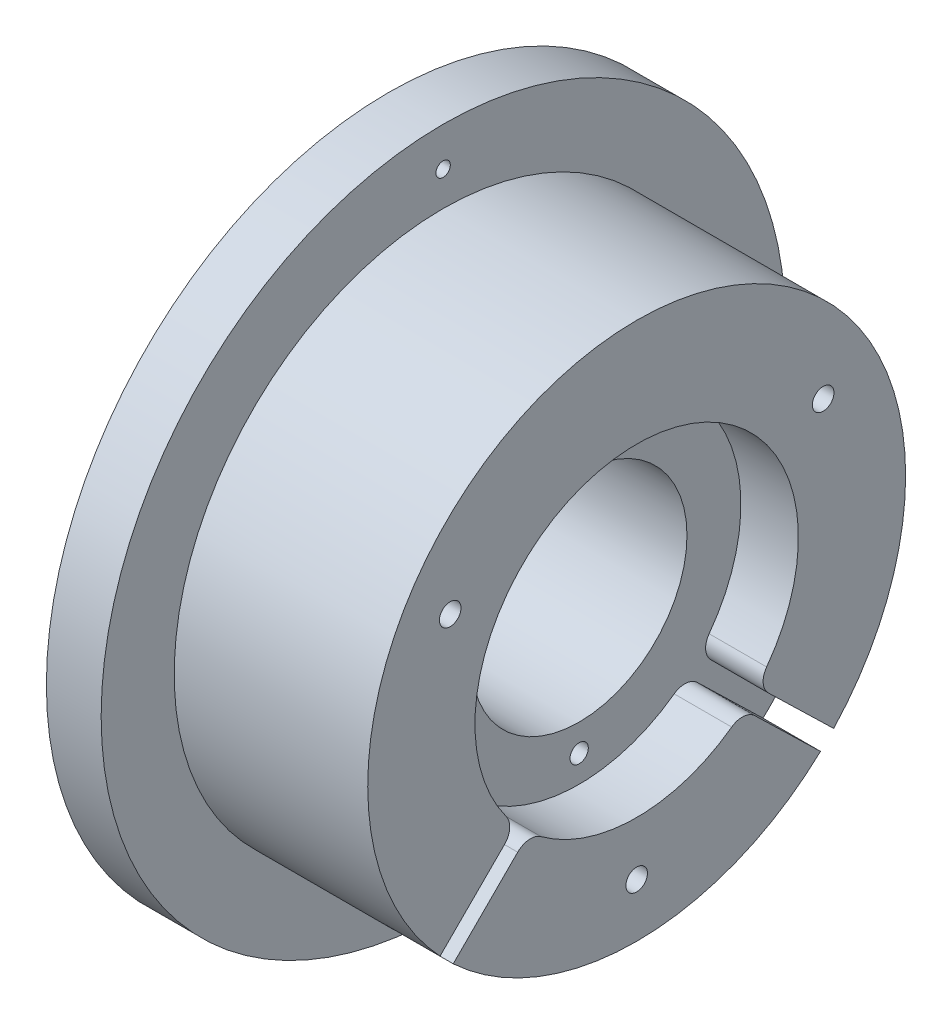
SolidWorks part; units mm, degrees
ref_plane "Front" through (0, 0, 0) normal (0, 0, 1) x (1, 0, 0)
ref_plane "Top" through (0, 0, 0) normal (0, 1, 0) x (1, 0, 0)
ref_plane "Right" through (0, 0, 0) normal (1, 0, 0) x (0, 0, -1)
sketch "Sketch1" plane through (0, 0, 0) normal (0, 0, 1) x (1, 0, 0)
  line L0 (0, 0) -> (0, 23.7871)
  line L1 (0, 23.7871) -> (3.81, 23.7871)
  line L2 (3.81, 23.7871) -> (3.81, 18.7071)
  line L3 (3.81, 18.7071) -> (17.272, 18.7071)
  line L4 (17.272, 18.7071) -> (17.272, 11.25)
  line L5 (17.272, 11.25) -> (13.272, 11.25)
  line L6 (13.272, 11.25) -> (13.272, 0)
  line L7 (13.272, 0) -> (0, 0)
  line L8 (13.272, 7.5) -> (0, 7.5)
  dimension "D1" = 23.7871
  dimension "D2" = 3.81
  dimension "D3" = 13.462
  dimension "D4" = 4
  dimension "D5" = 11.25
  dimension "D6" = 18.7071
  dimension "D7" = 7.5
revolve "Revolve1" add sketch "Sketch1" angle 360 about L7 region at (7.4749, 14.1825, 0)
sketch "Sketch2" plane through (17.272, 0, 0) normal (1, 0, 0) x (0, 0, -1)
  line L0 (0, 0) -> (-13.2279, -13.2279) construction
  line L1 (0, 0) -> (0, -18.7071) construction
  line L2 (0.2823, 0.2909) -> (13.7078, -12.7364)
  line L3 (-13.6875, -12.7683) -> (-12.7683, -13.6875)
  line L4 (-13.6875, -12.7683) -> (-0.4596, 0.4596)
  line L5 (-0.4596, 0.4596) -> (0.4596, -0.4596)
  line L6 (0.4596, -0.4596) -> (-12.7683, -13.6875)
  line L7 (12.8025, -13.6694) -> (13.7078, -12.7364)
  line L8 (12.8025, -13.6694) -> (-0.623, -0.642)
  line L9 (-0.623, -0.642) -> (0.2823, 0.2909)
  circle A0 centre (0, 0) radius 18.7071 construction
  circle A1 centre (-12.9709, 7.4887) radius 0.75
  circle A2 centre (12.9709, 7.4888) radius 0.75
  circle A3 centre (0, 0) radius 18.7071 construction
  circle A4 centre (0, -14.9775) radius 0.75
  point P6 (0, 0)
  point P14 (-13.2279, -13.2279)
  circle M8 centre (0, 0) radius 18.7071
  circle M9 centre (0, 0) radius 11.25
  dimension "D4" = 1.5
  dimension "D1" = 45
  dimension "D2" = 1.3
  dimension "D3" = 14.9775
  dimension "D5" = 3
  dimension "D6" = 2
extrude "Cut-Extrude1" cut sketch "Sketch2" against normal up to surface (4 mm away) contours L8 L9 L5 L4 L6 M9 | L6 L4 M9 M8 | L8 L2 M8 M9 | L9 L5 L6 L8 L2 M9 | A4 | A1 | A2 region at (17.272, -4.2339, -4.0243) region at (17.272, -10.6015, -10.574) region at (17.272, -4.115, 4.1339) region at (17.272, -10.5879, 10.5879) region at (17.272, 7.4887, 12.9709) region at (17.272, 7.4888, -12.9709) region at (17.272, -14.9775, 0) up to face at (13.272, 7.5, 0)
sketch "Sketch3" plane through (3.81, 0, 0) normal (1, 0, 0) x (0, 0, -1)
  line L0 (0, 0) -> (0, 21.082) construction
  circle A0 centre (0, 21.082) radius 0.5
  dimension "D1" = 1
  dimension "D2" = 21.082
extrude "Cut-Extrude2" cut sketch "Sketch3" against normal through all
sketch "Sketch4" plane through (13.272, 0, 0) normal (1, 0, 0) x (0, 0, -1)
  line L0 (0, -9.375) -> (0, 9.375) construction
  circle A0 centre (0, 9.375) radius 0.635
  circle A1 centre (0, -9.375) radius 0.635
  point P6 (0, 0)
  dimension "D2" = 1.27
  dimension "D1" = 18.75
extrude "Cut-Extrude3" cut sketch "Sketch4" against normal through all
fillet "Fillet1" radius 1.25 4 edges at (15.272, -7.482, 8.4013) (15.272, -8.4013, 7.482) (15.272, -8.4516, -7.4252) (15.272, -7.5383, -8.3508)
